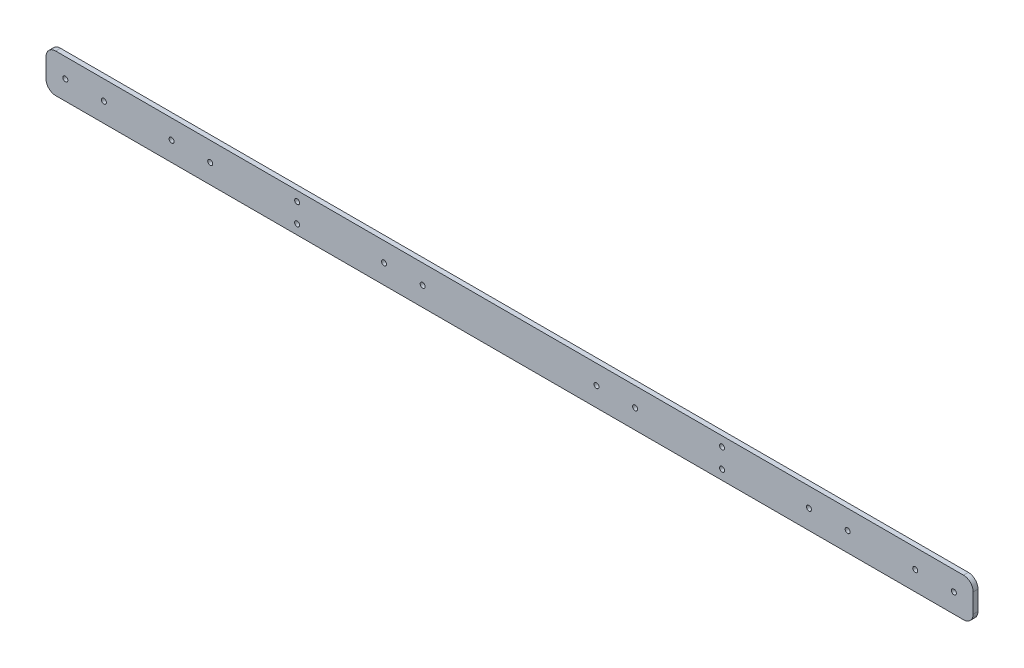
SolidWorks part; units mm, degrees
material "Maple"
ref_plane "Front" through (0, 0, 0) normal (0, 0, 1) x (1, 0, 0)
ref_plane "Top" through (0, 0, 0) normal (0, 1, 0) x (1, 0, 0)
ref_plane "Right" through (0, 0, 0) normal (1, 0, 0) x (0, 0, -1)
sketch "Sketch2" plane through (0, 0, 0) normal (0, 0, 1) x (1, 0, 0)
  line L0 (-292.1, 0) -> (-266.7, 0) construction
  line L1 (-298.45, 12.7) -> (298.45, 12.7)
  line L2 (-304.8, 6.35) -> (-304.8, -6.35)
  line L3 (-298.45, -12.7) -> (298.45, -12.7)
  line L4 (304.8, 6.35) -> (304.8, -6.35)
  line L5 (-304.8, 12.7) -> (304.8, -12.7) construction
  line L6 (-304.8, -12.7) -> (304.8, 12.7) construction
  line L7 (0, 12.7) -> (0, -12.7) construction
  arc A0 (298.45, 12.7) -> (304.8, 6.35) centre (298.45, 6.35) cw
  arc A1 (298.45, -12.7) -> (304.8, -6.35) centre (298.45, -6.35) ccw
  arc A2 (-304.8, -6.35) -> (-298.45, -12.7) centre (-298.45, -6.35) ccw
  arc A3 (-298.45, 12.7) -> (-304.8, 6.35) centre (-298.45, 6.35) ccw
  circle A4 centre (-292.1, 0) radius 1.6383
  circle A5 centre (-266.7, 0) radius 1.6383
  circle A6 centre (292.1, 0) radius 1.6383
  circle A7 centre (266.7, 0) radius 1.6383
  point P0 (0, 0)
  point P18 (-279.4, 0)
  dimension "D3" = 6.35
  dimension "D4" = 3.2766
  dimension "D1" = 609.6
  dimension "D2" = 25.4
  dimension "D5" = 25.4
  dimension "D6" = 558.8
extrude "Boss-Extrude1" add sketch "Sketch2" along normal blind 3.175
sketch "Sketch5" plane through (0, 0, 3.175) normal (0, 0, 1) x (1, 0, 0)
  line L0 (-222.25, 0) -> (-196.85, 0) construction
  line L1 (-82.55, 0) -> (-57.15, 0) construction
  line L2 (57.15, 0) -> (82.55, 0) construction
  line L3 (196.85, 0) -> (222.25, 0) construction
  line L4 (0, 0) -> (0, -12.7) construction
  line L5 (-298.45, -12.7) -> (298.45, -12.7) construction
  line L6 (-139.7, 6.35) -> (-139.7, -6.35) construction
  line L7 (139.7, 6.35) -> (139.7, -6.35) construction
  circle A0 centre (-222.25, 0) radius 1.6383
  circle A1 centre (-196.85, 0) radius 1.6383
  circle A2 centre (-82.55, 0) radius 1.6383
  circle A3 centre (-57.15, 0) radius 1.6383
  circle A4 centre (57.15, 0) radius 1.6383
  circle A5 centre (82.55, 0) radius 1.6383
  circle A6 centre (196.85, 0) radius 1.6383
  circle A7 centre (222.25, 0) radius 1.6383
  circle A8 centre (-139.7, 6.35) radius 1.6383
  circle A9 centre (-139.7, -6.35) radius 1.6383
  circle A10 centre (139.7, -6.35) radius 1.6383
  circle A11 centre (139.7, 6.35) radius 1.6383
  point P25 (-139.7, 0)
  point P30 (139.7, 0)
  dimension "D1" = 3.2766
  dimension "D6" = 3.2766
  dimension "D2" = 25.4
  dimension "D3" = 4
  dimension "D4" = 139.7
  dimension "D5" = 12.7
  dimension "D7" = 279.4
extrude "Cut-Extrude1" cut sketch "Sketch5" against normal through all
other "Flex1" [suppressed] parameters "D0"=49.091, "D1"=0, "D2"=0
ref_axis "Axis1" through (0, -13.058, -709.8988) along (0, 1, 0)
